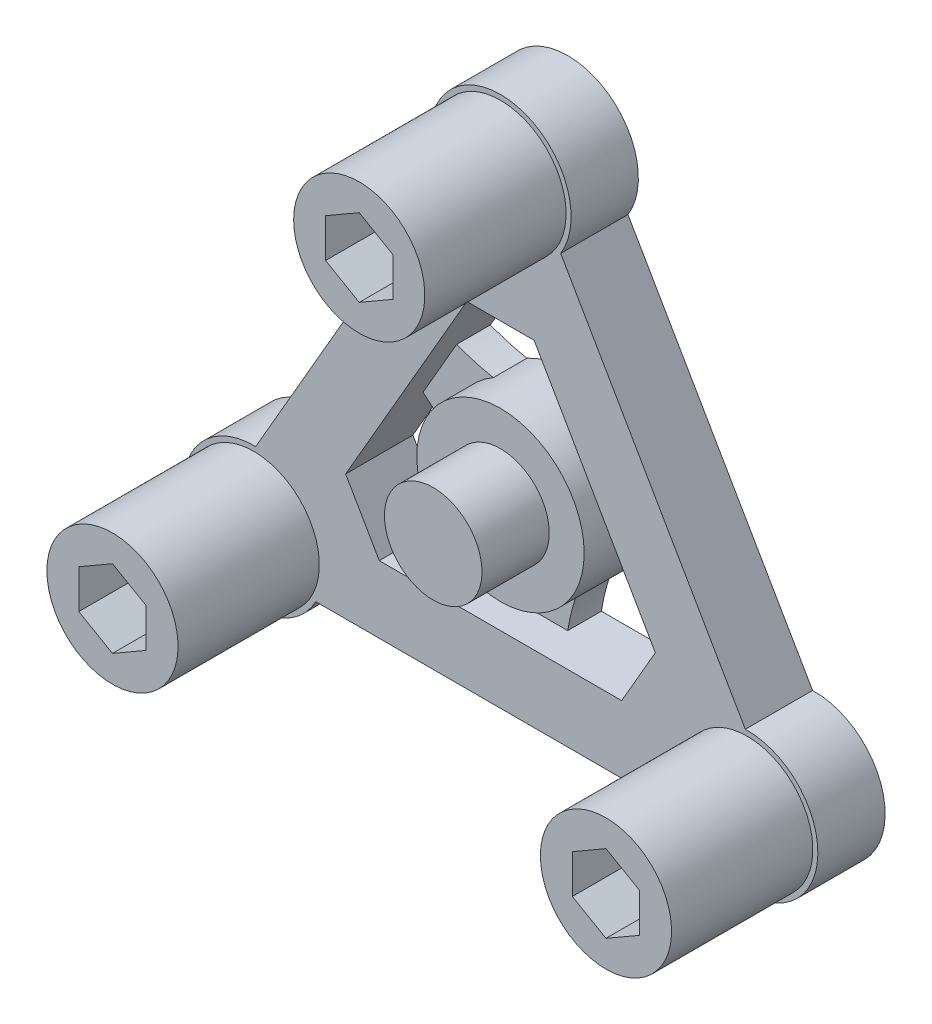
SolidWorks part; units mm, degrees
note: The reader was unsure of these and kept them because the rebuilt part matched: shared geometry of "Sketch5<3>".
ref_plane "Front Plane" through (0, 0, 0) normal (0, 0, 1) x (1, 0, 0)
ref_plane "Top Plane" through (0, 0, 0) normal (0, 1, 0) x (1, 0, 0)
ref_plane "Right Plane" through (0, 0, 0) normal (1, 0, 0) x (0, 0, -1)
sketch "Sketch1" plane through (0, 0, 0) normal (0, 0, 1) x (1, 0, 0)
  line L0 (0, 21.1785) -> (0, 0) construction
  line L1 (0, 0) -> (18.3411, -10.5892) construction
  line L2 (0, 0) -> (-18.3411, -10.5892) construction
  line L3 (0, 21.1785) -> (0, 42.357) construction
  line L4 (0, -55) -> (0, 55) construction
  line L5 (18.3411, -10.5892) -> (36.6822, -21.1785) construction
  line L6 (-18.3411, -10.5892) -> (-36.6822, -21.1785) construction
  circle A0 centre (0, 0) radius 21.1785 construction
  circle A1 centre (0, 42.357) radius 21.1785 construction
  circle A2 centre (36.6822, -21.1785) radius 21.1785 construction
  circle A3 centre (-36.6822, -21.1785) radius 21.1785 construction
  dimension "D3" = 42.357
  dimension "D4" = 42.357
  dimension "D1" = 120
  dimension "D2" = 120
sketch "Sketch2" plane through (0, 0, 0) normal (0, 0, 1) x (1, 0, 0)
  line L0 (-36.6822, -21.1785) -> (0, 42.357) construction
  line L1 (0, 42.357) -> (36.6822, -21.1785) construction
  line L2 (36.6822, -21.1785) -> (-36.6822, -21.1785) construction
  line L4 (-45.3425, -26.1785) -> (0, 52.357)
  line L7 (0, 32.357) -> (-28.022, -16.1785)
  line L8 (0, 21.1785) -> (0, 42.357) construction
  line L9 (0, 32.357) -> (28.022, -16.1785)
  line L10 (18.3411, -10.5892) -> (36.6822, -21.1785) construction
  line L11 (28.022, -16.1785) -> (-28.022, -16.1785)
  line L12 (-18.3411, -10.5892) -> (-36.6822, -21.1785) construction
  line L13 (0, -55) -> (0, 55) construction
  line L14 (0, 52.357) -> (45.3425, -26.1785)
  line L15 (45.3425, -26.1785) -> (-45.3425, -26.1785)
  line L16 (-22.6712, 13.0893) -> (-14.011, 8.0893) construction
  circle A3 centre (0, 42.357) radius 10.5
  circle A4 centre (36.6822, -21.1785) radius 10.5
  circle A5 centre (-36.6822, -21.1785) radius 10.5
  point P23 (-18.3411, 10.5893)
  point P24 (-18.3411, 10.5893)
  dimension "D2" = 21
  dimension "D1" = 10
extrude "Boss-Extrude1" add sketch "Sketch2" along normal mid plane 10 contours L4 A5 L15 | L14 A3 L4 | L15 A4 L14 | L9 A4 L11 | L11 A5 L7 | L7 A3 L9
sketch "Sketch3" plane through (0, 0, 0) normal (0, 0, 1) x (1, 0, 0)
  line L0 (-14.011, 8.0893) -> (0, 0) construction
  line L1 (28.022, -16.1785) -> (-28.022, -16.1785) construction
  line L2 (0, 0) -> (0, -16.1785) construction
  line L4 (0, 0) -> (14.011, 8.0893) construction
  line L6 (-16.511, 3.7591) -> (-11.511, 12.4194)
  line L7 (11.511, 12.4194) -> (16.511, 3.7591)
  line L8 (-5, -16.1785) -> (5, -16.1785)
  line L9 (0, 32.357) -> (28.022, -16.1785) construction
  line L10 (0, 32.357) -> (-28.022, -16.1785) construction
  arc A0 (-16.511, 3.7591) -> (-5, -16.1785) centre (-36.6822, -21.1785) cw
  arc A1 (5, -16.1785) -> (16.511, 3.7591) centre (36.6822, -21.1785) cw
  arc A2 (-11.511, 12.4194) -> (11.511, 12.4194) centre (0, 42.357) ccw
  point P14 (-14.011, 8.0893)
  point P17 (14.011, 8.0893)
  point P20 (0, -16.1785)
  dimension "D1" = 10
extrude "Boss-Extrude2" add sketch "Sketch3" against normal up to surface (5 mm away) up to face at (0, 0, -5)
sketch "Sketch4" plane through (0, 0, 5) normal (0, 0, 1) x (1, 0, 0)
  circle A0 centre (-36.6822, -21.1785) radius 9.75
  circle A1 centre (36.6822, -21.1785) radius 9.75
  circle A2 centre (0, 42.357) radius 9.75
  dimension "D1" = 19.5
extrude "Boss-Extrude3" add sketch "Sketch4" along normal blind 21
sketch "Sketch5" plane through (0, 0, 0) normal (0, 0, 1) x (1, 0, 0)
  circle A0 centre (0, 0) radius 7.25
  circle A1 centre (0, 0) radius 12.4416
  dimension "D1" = 14.5
extrude "Boss-Extrude4" add sketch "Sketch5" along normal up to surface and the other way up to surface contours A1
extrude "Boss-Extrude5" add sketch "Sketch5<3>" along normal offset from surface (15 mm away) 10 contours A0 up to face at (12.4416, 0, 5) offset beyond the face yes
sketch "Sketch5<3>" plane through (0, 0, 0) normal (0, 0, 1) x (1, 0, 0) same geometry as "Sketch5"
chamfer "Chamfer1" distance 10 3 edges at (0, 32.357, 0) (-28.022, -16.1785, 0) (28.022, -16.1785, 0)
sketch "Sketch8" plane through (0, 0, 26) normal (0, 0, 1) x (1, 0, 0)
  line L1 (-41.6822, -24.0653) -> (-36.6822, -26.952)
  line L2 (-36.6822, -26.952) -> (-31.6822, -24.0653)
  line L3 (-31.6822, -24.0653) -> (-31.6822, -18.2917)
  line L4 (-31.6822, -18.2917) -> (-36.6822, -15.405)
  line L5 (-36.6822, -15.405) -> (-41.6822, -18.2917)
  line L6 (-41.6822, -18.2917) -> (-41.6822, -24.0653)
  line L7 (41.6822, -24.0653) -> (41.6822, -18.2917)
  line L8 (41.6822, -18.2917) -> (36.6822, -15.405)
  line L9 (36.6822, -15.405) -> (31.6822, -18.2917)
  line L10 (31.6822, -18.2917) -> (31.6822, -24.0653)
  line L11 (31.6822, -24.0653) -> (36.6822, -26.952)
  line L12 (36.6822, -26.952) -> (41.6822, -24.0653)
  line L13 (0, 48.1305) -> (-5, 45.2438)
  line L14 (-5, 45.2438) -> (-5, 39.4702)
  line L15 (-5, 39.4702) -> (0, 36.5835)
  line L16 (0, 36.5835) -> (5, 39.4702)
  line L17 (5, 39.4702) -> (5, 45.2438)
  line L18 (5, 45.2438) -> (0, 48.1305)
  circle A0 centre (-36.6822, -21.1785) radius 5 construction
  circle A1 centre (36.6822, -21.1785) radius 5 construction
  circle A2 centre (0, 42.357) radius 5 construction
  dimension "D1" = 10
extrude "Cut-Extrude1" cut sketch "Sketch8" against normal blind 10
sketch "Sketch10" plane through (0, 0, -5) normal (0, 0, -1) x (-1, 0, 0)
  line L1 (9.3819, 0) -> (4.691, 8.125)
  line L2 (4.691, 8.125) -> (-4.691, 8.125)
  line L3 (-4.691, 8.125) -> (-9.3819, 0)
  line L4 (-9.3819, 0) -> (-4.691, -8.125)
  line L5 (-4.691, -8.125) -> (4.691, -8.125)
  line L6 (4.691, -8.125) -> (9.3819, 0)
  circle A0 centre (0, 0) radius 8.125 construction
  dimension "D1" = 16.25
extrude "Cut-Extrude2" cut sketch "Sketch10" against normal blind 4.2
equation "\"sN\"= 12'Sun teeth"
equation "\"rN\"= 36'Ring teeth"
equation "\"pN\"= ( \"rN\" - \"sN\" ) / 2'Planet teeth"
equation "\"m\"= 3.5'Modulus"
equation "\"sRD\"= \"sN\" * \"m\"'Sun root diam"
equation "\"rRD\"= \"rN\" * \"m\"'Ring root diam"
equation "\"pRD\"= \"pN\" * \"m\"'Planet root diam"
equation "\"D3@Sketch1\"=\"sRD\"*\"sF\""
equation "\"D4@Sketch1\"=\"pRD\"*\"sF\""
equation "\"D2@Sketch2\"=\"pRD\"*0.5"
equation "\"sF\"= 1.0085"
